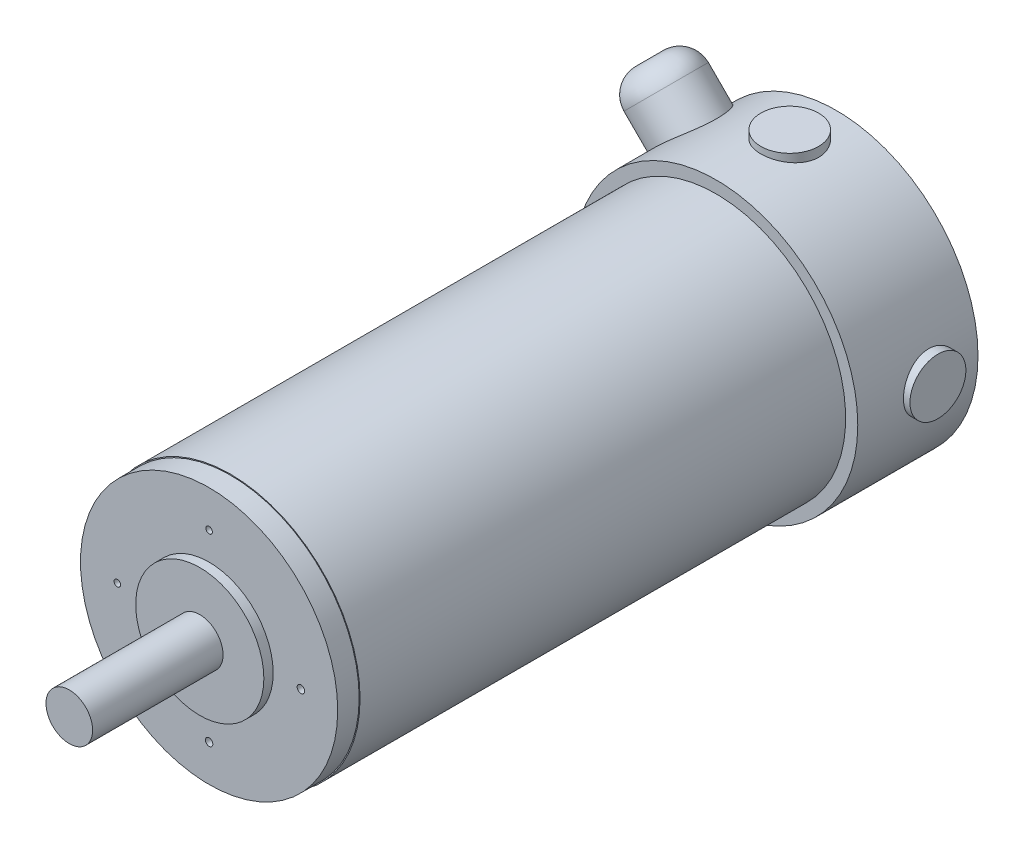
SolidWorks part; units mm, degrees
ref_plane "Plane1" through (0, 0, 0) normal (0, 0, 1) x (1, 0, 0)
ref_plane "Plane2" through (0, 0, 0) normal (0, 1, 0) x (1, 0, 0)
ref_plane "Plane3" through (0, 0, 0) normal (1, 0, 0) x (0, 0, -1)
sketch "Sketch1" plane through (0, 0, 0) normal (0, 0, 1) x (1, 0, 0)
  circle A0 centre (0, 0) radius 35.306
  circle A2 centre (25.019, 0) radius 1.016
  circle A3 centre (0, 25.019) radius 1.016
  circle A4 centre (-25.019, 0) radius 1.016
  circle A5 centre (0, -25.019) radius 1.016
extrude "Base-Extrude" add sketch "Sketch1" along normal blind 165.1
sketch "Sketch2" plane through (0, 0, 0) normal (0, 0, -1) x (-1, 0, 0)
  circle A0 centre (0, 0) radius 38.608
extrude "Boss-Extrude1" add sketch "Sketch2" against normal blind 32.766
sketch "Sketch3" plane through (0, 0, 165.1) normal (0, 0, 1) x (1, 0, 0)
  circle A0 centre (0, 0) radius 6.35
extrude "Boss-Extrude2" add sketch "Sketch3" along normal blind 43.942
sketch "Sketch4" plane through (0, 0, 165.1) normal (0, 0, 1) x (1, 0, 0)
  circle A0 centre (0, 0) radius 17.4625
extrude "Boss-Extrude3" add sketch "Sketch4" along normal blind 8.382
sketch "Sketch5" plane through (0, 0, 165.1) normal (0, 0, 1) x (1, 0, 0)
  circle A0 centre (0, 0) radius 35.306
sketch "Sketch6" plane through (0, 0, 209.042) normal (0, 0, 1) x (1, 0, 0)
  point P0 (0, 0)
  point P1 (0, 25.019)
ref_plane "Plane4" through (0, 0, 0) normal (1, 0, 0) x (0, 0, -1)
sketch "Sketch7" plane through (0, 0, 0) normal (1, 0, 0) x (0, 0, -1)
  circle A0 centre (-12.7, 0) radius 7.874
extrude "Boss-Extrude5" add sketch "Sketch7" against normal blind 40.386
sketch "Sketch9" plane through (-40.386, 0, 0) normal (-1, 0, 0) x (0, 0, 1)
  circle A0 centre (12.7, 0) radius 7.62
extrude "Boss-Extrude7" add sketch "Sketch9" against normal blind 80.772
sketch "Sketch10" plane through (0, 0, 165.1) normal (0, 0, 1) x (1, 0, 0)
  point P0 (-25.019, 0)
ref_plane "Plane5" through (0, 0, 0) normal (0, 1, 0) x (-1, 0, 0)
sketch "Sketch11" plane through (0, 0, 0) normal (0, 1, 0) x (-1, 0, 0)
  line L2 (0, 12.5095) -> (0, -12.5095) construction
  circle A0 centre (0, 12.7) radius 7.874
extrude "Boss-Extrude8" add sketch "Sketch11" along normal blind 40.386
sketch "Sketch12" plane through (0, 40.386, 0) normal (0, 1, 0) x (-1, 0, 0)
  line L0 (0, 12.5095) -> (0, -12.5095) construction
  circle A1 centre (0, 12.7) radius 7.874
extrude "Boss-Extrude10" add sketch "Sketch12" against normal blind 80.772
ref_axis "Axis1" through (0, 0, -50) along (0, 0, 1)
ref_plane "Plane6" through (0, 0, 0) normal (-0.7071, 0.7071, 0) x (0, 0, 1)
sketch "Sketch13" plane through (0, 0, 0) normal (-0.7071, 0.7071, 0) x (0, 0, 1)
  circle A0 centre (12.7, 0) radius 9.398
extrude "Boss-Extrude11" add sketch "Sketch13" along normal blind 53.975
fillet "Fillet1" radius 6.35 1 edges at (-44.8115, 31.5207, 12.7)
sketch "Sketch14" plane through (0, 0, 0) normal (0, 0, -1) x (-1, 0, 0)
  circle A0 centre (0, 0) radius 6.35
extrude "Boss-Extrude12" add sketch "Sketch14" along normal blind 16.002
sketch "Sketch15" plane through (0, 0, 165.1) normal (0, 0, 1) x (1, 0, 0)
  circle A0 centre (0, 0) radius 35.052
  circle A1 centre (25.019, 0) radius 1.016
  circle A2 centre (0, 25.019) radius 0.889
  circle A3 centre (0, -25.019) radius 1.016
  circle A4 centre (-25.019, 0) radius 0.889
  point P6 (0, 25.019)
  point P10 (0, -25.019)
  point P14 (-25.019, 0)
extrude "Boss-Extrude13" add sketch "Sketch15" along normal blind 5.842
